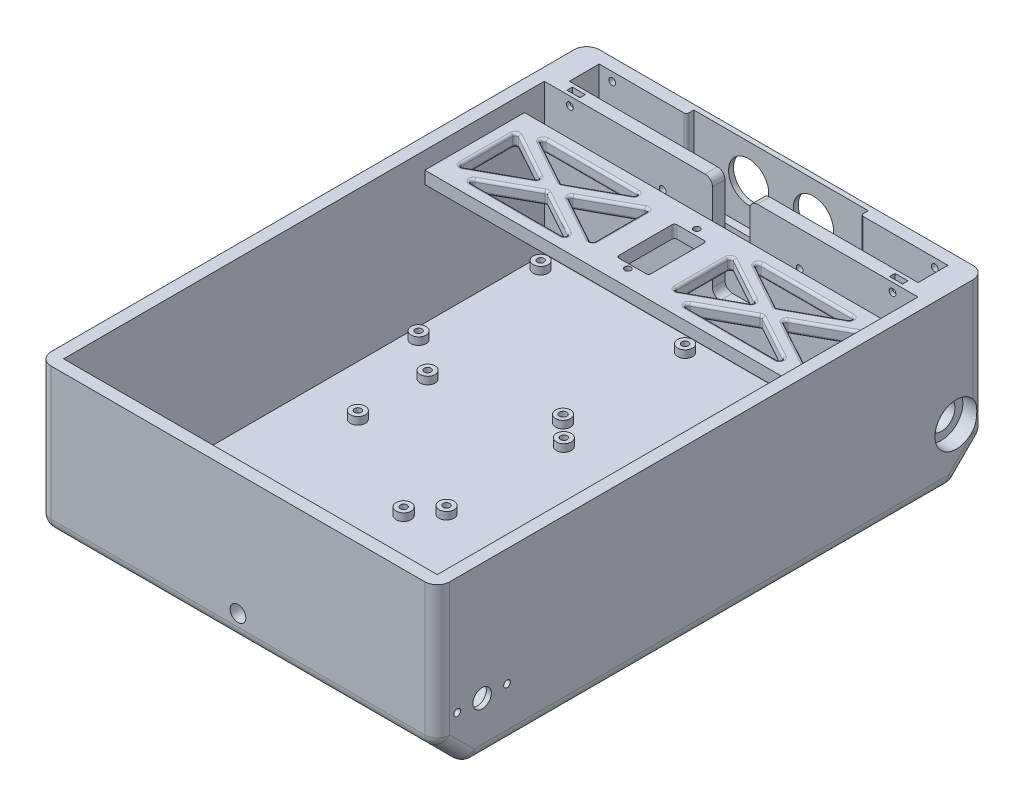
SolidWorks part; units mm, degrees
ref_plane "Front Plane" through (0, 0, 0) normal (0, 0, 1) x (1, 0, 0)
ref_plane "Top Plane" through (0, 0, 0) normal (0, 1, 0) x (1, 0, 0)
ref_plane "Right Plane" through (0, 0, 0) normal (1, 0, 0) x (0, 0, -1)
sketch "Main Body" plane through (0, 0, 0) normal (0, 1, 0) x (1, 0, 0)
  line L0 (-75, 110) -> (75, 110)
  line L1 (-75, -105) -> (75, -105)
  line L2 (-75, -105) -> (-75, 105)
  line L3 (-75, 105) -> (75, 105)
  line L4 (75, -105) -> (75, 105)
  line L5 (-75, -105) -> (75, 105) construction
  line L6 (-75, 105) -> (75, -105) construction
  line L7 (80, -105) -> (80, 105)
  line L8 (-75, -110) -> (75, -110)
  line L9 (-80, -105) -> (-80, 105)
  line L10 (-80, -110) -> (80, -110) construction
  line L11 (-80, -110) -> (-80, 110) construction
  line L12 (80, -110) -> (80, 110) construction
  line L13 (-80, 110) -> (80, 110) construction
  arc A0 (-75, -110) -> (-80, -105) centre (-75, -105) cw
  arc A1 (80, -105) -> (75, -110) centre (75, -105) cw
  arc A2 (75, 110) -> (80, 105) centre (75, 105) cw
  arc A3 (-75, 110) -> (-80, 105) centre (-75, 105) ccw
  point P0 (0, 0)
  dimension "D4" = 5
  dimension "D1" = 75
  dimension "D2" = 210
  dimension "D3" = 5
extrude "Boss-Extrude1" add sketch "Main Body" along normal blind 8 contours L1 L4 L3 L2 | L9 L8 L7 L0 L4 L1 L2 L3 region at (0, 0, -107.2797) region at (0, 0, 0)
extrude "Boss-Extrude3" add sketch "Main Body<4>" along normal blind 60 from surface starting at face at (0, 8, 0)
sketch "Main Body<4>" plane through (0, 0, 0) normal (0, 1, 0) x (1, 0, 0) same geometry as "Main Body"
sketch "Sketch1" plane through (75, 0, 0) normal (-1, 0, 0) x (0, 0, 1)
  line L0 (105, 68) -> (105, 8) construction
  line L1 (-105, 8) -> (105, 8) construction
  line L2 (79, 15.5) -> (105, 15.5)
  line L3 (79, 8) -> (105, 8)
  line L4 (79, 8) -> (79, 34)
  line L5 (79, 34) -> (105, 34)
  line L6 (105, 8) -> (105, 34)
  line L7 (79, 8) -> (105, 34) construction
  line L8 (79, 34) -> (105, 8) construction
  circle A0 centre (92, 21) radius 13
  line M2 (-105, 8) -> (105, 8)
  line M3 (105, 8) -> (105, 68)
  dimension "D1" = 26
  dimension "D2" = 7.5
extrude "Boss-Extrude4" add sketch "Sketch1" along normal up to surface (150 mm away) contours A0 L4 M2 | A0 L3 M3 region at (75, 10.5201, 82.0674) region at (75, 10.5201, 101.9326) up to face at (-75, 38, 0)
sketch "Sketch2" plane through (0, 0, 0) normal (1, 0, 0) x (0, 0, -1)
  line L0 (-105, 68) -> (-105, 15.5) construction
  line L1 (-105, 8) -> (-79, 8)
  line L2 (-105, 8) -> (-105, 15.5)
  line L3 (-105, 15.5) -> (-79, 15.5)
  line L4 (-79, 8) -> (-79, 15.5)
  line L5 (105, 8) -> (-79, 8) construction
  line L6 (-79, 8) -> (-79, 15.5) construction
  line L7 (-79, 15.5) -> (-80.2208, 15.5) construction
extrude "Cut-Extrude1" cut sketch "Sketch2" against normal mid plane 12
sketch "Sketch3" plane through (0, 8, 0) normal (0, 1, 0) x (1, 0, 0)
  line L0 (75, -105) -> (-75, -105) construction
  line L1 (-4, -79) -> (-11, -79)
  line L2 (-4, -79) -> (-4, -105)
  line L3 (-4, -105) -> (-11, -105)
  line L4 (-11, -79) -> (-11, -105)
  line L5 (0, 0) -> (0, -105) construction
  line L6 (-75, -79) -> (-6, -79) construction
  line L7 (11, -79) -> (11, -105)
  line L8 (4, -105) -> (11, -105)
  line L9 (4, -79) -> (4, -105)
  line L10 (4, -79) -> (11, -79)
  line L11 (-6, -103.7792) -> (-6, -92) construction
  dimension "D1" = 5
  dimension "D2" = 4
extrude "Boss-Extrude5" add sketch "Sketch3" along normal blind 20
sketch "Sketch4" plane through (0, 8, 0) normal (0, 1, 0) x (1, 0, 0)
  line L0 (-75, -105) -> (-75, 105) construction
  line L1 (-75, 93) -> (75, 93)
  line L2 (-75, 93) -> (-75, 88)
  line L3 (-75, 88) -> (75, 88)
  line L4 (75, 93) -> (75, 88)
  line L5 (75, 105) -> (75, -105) construction
  line L6 (-75, 105) -> (75, 105) construction
  dimension "D1" = 17
  dimension "D2" = 5
extrude "Boss-Extrude6" add sketch "Sketch4" along normal up to surface (60 mm away) up to face at (0, 68, 0)
sketch "Sketch5" plane through (80, 0, 0) normal (1, 0, 0) x (0, 0, -1)
  circle A0 centre (-92, 21) radius 3.5 construction
  circle A1 centre (-92, 21) radius 3.5
  circle A2 centre (-92, 21) radius 3.7
  dimension "D1" = 0.2
extrude "Cut-Extrude4" cut sketch "Sketch5" against normal up to next contours A1 | A2 A1 region at (80, 21, 92) region at (80, 21, 95.5953)
sketch "Sketch6" plane through (-75, 0, 0) normal (1, 0, 0) x (0, 0, -1)
  circle A0 centre (-92, 21) radius 13
  dimension "D1" = 26
extrude "Cut-Extrude5" cut sketch "Sketch6" against normal offset from surface (3 mm away) 2 up to face at (-80, 34, 0)
mirror "Mirror1" about plane through (0, 0, 0) normal (1, 0, 0) of "Cut-Extrude4"
sketch "Sketch8" plane through (75, 0, 0) normal (-1, 0, 0) x (0, 0, 1)
  circle A0 centre (92, 21) radius 13
  dimension "D1" = 26
extrude "Cut-Extrude6" cut sketch "Sketch8" against normal offset from surface (3 mm away) 2 up to face at (80, 21, 88.3)
sketch "Sketch10" plane through (80, 0, 0) normal (1, 0, 0) x (0, 0, -1)
  circle A1 centre (-82, 21) radius 1.25
  circle A2 centre (-82, 21) radius 1.25
  circle A3 centre (-102, 21) radius 1.25
  circle A4 centre (-102, 21) radius 1.25
  circle A5 centre (-92, 21) radius 12.5
  circle A6 centre (-92, 21) radius 12.5
  circle A63 centre (-102, 21) radius 1.35
  circle A64 centre (-82, 21) radius 1.35
  dimension "D4" = 2.7
extrude "Cut-Extrude7" cut sketch "Sketch10" against normal up to next contours A2 | A64 A2 | A4 | A63 A4 region at (80, 21, 82) region at (80, 21, 102) region at (80, 21, 103.3118) region at (80, 21, 83.3118)
mirror "Mirror3" about plane through (0, 0, 0) normal (1, 0, 0) of "Cut-Extrude7"
sketch "Sketch11" plane through (80, 0, 0) normal (1, 0, 0) x (0, 0, -1)
  circle A0 centre (98.375, 21.05) radius 4.425 construction
  circle A1 centre (98.375, 21.05) radius 4.425
  circle A3 centre (98.375, 21.05) radius 5.425
  dimension "D1" = 1
extrude "Cut-Extrude10" cut sketch "Sketch11" against normal through all contours A1 | A3 A1 region at (80, 21.05, -98.375) region at (80, 21.05, -93.1034)
sketch "Sketch12" plane through (-75, 0, 0) normal (1, 0, 0) x (0, 0, -1)
  line L0 (93, 8) -> (105, 8) construction
  line L1 (93, 68) -> (105, 68)
  line L2 (93, 68) -> (93, 8)
  line L3 (93, 8) -> (105, 8)
  line L4 (105, 68) -> (105, 8)
  line L6 (93, 68) -> (93, 21.7848) construction
  line L7 (93, 68) -> (105, 68) construction
  circle A2 centre (98.375, 21.05) radius 5.425 construction
  circle A3 centre (98.375, 21.05) radius 5.425
  point P5 (0, 0)
extrude "Boss-Extrude7" add sketch "Sketch12" along normal blind 5 contours A3 L2 L3 L4 L1 region at (-75, 40.4958, -99.0916)
sketch "Sketch13" plane through (-80, 0, 0) normal (-1, 0, 0) x (0, 0, 1)
  circle A0 centre (-98.375, 21.05) radius 8.6
  circle A2 centre (-98.375, 21.05) radius 5.425 construction
  dimension "D1" = 17.2
extrude "Cut-Extrude11" cut sketch "Sketch13" against normal blind 6
mirror "Mirror4" about plane through (0, 0, 0) normal (1, 0, 0) of "Boss-Extrude7", "Cut-Extrude11"
sketch "Sketch14" plane through (0, 8, 0) normal (0, 1, 0) x (1, 0, 0)
  line L0 (-4, -105) -> (-4, -79) construction
  line L1 (-4, -95) -> (4, -95)
  line L2 (-4, -95) -> (-4, -105)
  line L3 (-4, -105) -> (4, -105)
  line L4 (4, -95) -> (4, -105)
  dimension "D1" = 10
extrude "Boss-Extrude9" add sketch "Sketch14" along normal blind 5
sketch "Sketch15" plane through (0, 0, 110) normal (0, 0, 1) x (1, 0, 0)
  arc A4 (3.15, 19.5) -> (-3.15, 19.5) centre (0, 19.5) ccw
  arc A5 (-3.15, 19.5) -> (3.15, 19.5) centre (0, 19.5) ccw
  arc A6 (3, 19.5) -> (-3, 19.5) centre (0, 19.5) ccw construction
  dimension "D1" = 3.15
extrude "Cut-Extrude12" cut sketch "Sketch15" against normal up to next contours A4 A5 region at (0, 19.5, 110)
sketch "Sketch16" plane through (0, 0, 0) normal (0, -1, 0) x (1, 0, 0)
  circle A0 centre (-12.5, -82) radius 1.475 construction
  circle A1 centre (-70.5, -82) radius 1.475 construction
  circle A2 centre (-70.5, -33) radius 1.475 construction
  circle A3 centre (-12.5, -33) radius 1.475 construction
  circle A4 centre (-4.2, -25) radius 1.475 construction
  circle A5 centre (-55, -21.12) radius 1.475 construction
  circle A6 centre (-55, 6.88) radius 1.475 construction
  circle A7 centre (-4.2, 22.08) radius 1.475 construction
  circle A8 centre (-12.3, 31.18) radius 1.475 construction
  circle A9 centre (24.2, 31.18) radius 1.475 construction
  circle A10 centre (37.8459, 24.117) radius 1.475 construction
  circle A11 centre (59.5541, 24.117) radius 1.475 construction
  circle A12 centre (59.5541, 68.243) radius 1.475 construction
  circle A13 centre (37.8459, 68.243) radius 1.475 construction
  circle A14 centre (24.2, 67.68) radius 1.475 construction
  circle A15 centre (-12.3, 67.68) radius 1.475 construction
  circle A16 centre (-12.5, -82) radius 1.475
  circle A17 centre (-70.5, -82) radius 1.475
  circle A18 centre (-70.5, -33) radius 1.475
  circle A19 centre (-12.5, -33) radius 1.475
  circle A20 centre (-4.2, -25) radius 1.475
  circle A21 centre (-55, -21.12) radius 1.475
  circle A22 centre (-55, 6.88) radius 1.475
  circle A23 centre (-4.2, 22.08) radius 1.475
  circle A24 centre (-12.3, 31.18) radius 1.475
  circle A25 centre (24.2, 31.18) radius 1.475
  circle A26 centre (37.8459, 24.117) radius 1.475
  circle A27 centre (59.5541, 24.117) radius 1.475
  circle A28 centre (59.5541, 68.243) radius 1.475
  circle A29 centre (37.8459, 68.243) radius 1.475
  circle A30 centre (24.2, 67.68) radius 1.475
  circle A31 centre (-12.3, 67.68) radius 1.475
  circle A32 centre (-70.5, -82) radius 1.35
  circle A33 centre (-12.5, -82) radius 1.35
  circle A34 centre (-12.5, -33) radius 1.35
  circle A35 centre (-4.2, -25) radius 1.35
  circle A36 centre (-55, -21.12) radius 1.35
  circle A37 centre (-70.5, -33) radius 1.35
  circle A38 centre (-55, 6.88) radius 1.35
  circle A39 centre (-12.3, 31.18) radius 1.35
  circle A40 centre (-4.2, 22.08) radius 1.35
  circle A41 centre (24.2, 31.18) radius 1.35
  circle A42 centre (37.8459, 24.117) radius 1.35
  circle A43 centre (59.5541, 24.117) radius 1.35
  circle A44 centre (37.8459, 68.243) radius 1.35
  circle A45 centre (59.5541, 68.243) radius 1.35
  circle A46 centre (24.2, 67.68) radius 1.35
  circle A47 centre (-12.3, 67.68) radius 1.35
  dimension "D1" = 2.7
extrude "Cut-Extrude13" cut sketch "Sketch16" against normal up to next contours A47 | A46 | A44 | A45 | A35 | A37 | A36 | A38 | A39 | A40 | A41 | A42 | A43 | A32 | A33 | A19 region at (-70.5, 0, -82) region at (-12.5, 0, -82) region at (-4.2, 0, -25) region at (-55, 0, -21.12) region at (-70.5, 0, -33) region at (-55, 0, 6.88) region at (-12.3, 0, 31.18) region at (-4.2, 0, 22.08) region at (24.2, 0, 31.18) region at (37.8459, 0, 24.117) region at (59.5541, 0, 24.117) region at (37.8459, 0, 68.243) region at (59.5541, 0, 68.243) region at (24.2, 0, 67.68) region at (-12.3, 0, 67.68)
sketch "Sketch18" plane through (75, 0, 0) normal (-1, 0, 0) x (0, 0, 1)
  line L1 (-80, 61.1) -> (-40, 61.1)
  line L2 (-80, 61.1) -> (-80, 56.1)
  line L3 (-80, 56.1) -> (-40, 56.1)
  line L4 (-40, 61.1) -> (-40, 56.1)
  line L5 (-88, 68) -> (105, 68) construction
  dimension "D1" = 5
  dimension "D2" = 30
  dimension "D3" = 40
  dimension "D4" = 6.9
extrude "Boss-Extrude11" add sketch "Sketch18" along normal up to next
sketch "Sketch19" plane through (0, 68, 0) normal (0, 1, 0) x (1, 0, 0)
  line L1 (-6.425, 71.625) -> (6.425, 71.625)
  line L2 (-6.425, 71.625) -> (-6.425, 48.375)
  line L3 (-6.425, 48.375) -> (6.425, 48.375)
  line L4 (6.425, 71.625) -> (6.425, 48.375)
  line L12 (-75, 80) -> (-75, 40)
  line L13 (-75, 40) -> (75, 40)
  line L14 (75, 40) -> (75, 80)
  line L15 (75, 80) -> (-75, 80)
  line L16 (-75, 80) -> (-75, 40)
  line L17 (-75, 40) -> (75, 40)
  line L18 (75, 40) -> (75, 80)
  line L19 (75, 80) -> (-75, 80)
  point P4 (0, 71.625)
  point P8 (0, 80)
  point P12 (6.425, 60)
  point P13 (75, 60)
  dimension "D1" = 23.25
  dimension "D2" = 12.85
  dimension "D3" = 0
extrude "Cut-Extrude14" cut sketch "Sketch19" against normal up to next contours L4 L1 L2 L3 region at (0, 68, -60)
sketch "Sketch21" plane through (0, 0, -110) normal (0, 0, -1) x (-1, 0, 0)
  circle A1 centre (-64.75, 64.5) radius 1.3
  circle A2 centre (-64.75, 64.5) radius 1.3
  circle A3 centre (64.75, 64.5) radius 1.3
  circle A4 centre (64.75, 64.5) radius 1.3
  circle A44 centre (-64.75, 64.5) radius 1.35
  circle A45 centre (64.75, 64.5) radius 1.35
  dimension "D3" = 2.7
extrude "Cut-Extrude16" cut sketch "Sketch21" against normal up to surface (22 mm away) contours A44 A2 | A2 | A45 A4 | A4 region at (64.75, 64.5, -110) region at (-64.75, 64.5, -110) region at (66.0618, 64.5, -110) region at (-63.4382, 64.5, -110) up to face at (0, 38, -88)
ref_plane "Plane1" through (0, 0, -90.5) normal (0, 0, -1) x (-1, 0, 0)
sketch "Sketch22" plane through (0, 0, -90.5) normal (0, 0, -1) x (-1, 0, 0)
  line L0 (-67.35, 66.0011) -> (-67.35, 68)
  line L1 (-62.15, 66.0011) -> (-64.75, 67.5022)
  line L2 (-64.75, 67.5022) -> (-67.35, 66.0011)
  line L3 (-67.35, 66.0011) -> (-67.35, 62.9989)
  line L4 (-67.35, 62.9989) -> (-64.75, 61.4978)
  line L5 (-64.75, 61.4978) -> (-62.15, 62.9989)
  line L6 (-62.15, 62.9989) -> (-62.15, 66.0011)
  line L7 (-67.35, 68) -> (-62.15, 68)
  line L8 (-62.15, 68) -> (-62.15, 66.0011)
  line L9 (70, 68) -> (-70, 68) construction
  line L10 (0, 0) -> (0, 68) construction
  line L11 (75, 68) -> (-75, 68) construction
  line L12 (64.75, 61.4978) -> (62.15, 62.9989)
  line L13 (67.35, 62.9989) -> (64.75, 61.4978)
  line L14 (64.75, 67.5022) -> (67.35, 66.0011)
  line L15 (67.35, 66.0011) -> (67.35, 62.9989)
  line L16 (67.35, 66.0011) -> (67.35, 68)
  line L17 (62.15, 62.9989) -> (62.15, 66.0011)
  line L18 (62.15, 68) -> (62.15, 66.0011)
  line L19 (67.35, 68) -> (62.15, 68)
  line L20 (62.15, 66.0011) -> (64.75, 67.5022)
  circle A0 centre (-64.75, 64.5) radius 2.6 construction
  circle A1 centre (-64.75, 64.5) radius 1.35 construction
  dimension "D1" = 5.2
extrude "Cut-Extrude17" cut sketch "Sketch22" against normal mid plane 2.2 contours L20 L17 L12 L13 L15 L14 | L18 L20 L14 L16 L19 | L5 L6 L1 L2 L3 L4 | L8 L7 L0 L2 L1 region at (67.2943, 67.0006, -90.5) region at (64.75, 64.5, -90.5) region at (-64.75, 64.5, -90.5) region at (-62.2057, 67.0006, -90.5)
sketch "Sketch23" plane through (0, 0, -110) normal (0, 0, -1) x (-1, 0, 0)
  circle A0 centre (64.75, 64.5) radius 2.5
  circle A1 centre (-64.75, 64.5) radius 2.5
  circle A2 centre (64.75, 64.5) radius 1.35 construction
  circle A3 centre (-64.75, 64.5) radius 1.35 construction
  dimension "D1" = 5
  dimension "D2" = 5
extrude "Cut-Extrude18" cut sketch "Sketch23" against normal mid plane 2.5
sketch "Sketch24" plane through (0, 61.1, 0) normal (0, 1, 0) x (1, 0, 0)
  circle A0 centre (0, 46.475) radius 1.2502
  arc A1 (0.4, 45.5583) -> (-0.4, 45.5583) centre (0, 46.475) ccw construction
  circle A2 centre (0, 74.175) radius 1.2502
  arc A3 (-0.4, 75.0917) -> (0, 73.1748) centre (0, 74.175) ccw construction
  point P5 (0.4, 45.5583)
  dimension "D1" = 0.25
extrude "Cut-Extrude19" cut sketch "Sketch24" against normal up to next
sketch "Sketch25" plane through (0, 61.1, 0) normal (0, 1, 0) x (1, 0, 0)
  line L1 (-11.3, 80) -> (11.3, 80)
  line L2 (-11.3, 80) -> (-11.3, 40)
  line L3 (-11.3, 40) -> (11.3, 40)
  line L4 (-75, 80) -> (-75, 40)
  line L5 (-75, 40) -> (75, 40)
  line L6 (75, 40) -> (75, 80)
  line L7 (75, 80) -> (-75, 80)
  line L8 (-75, 80) -> (-75, 40)
  line L9 (-75, 40) -> (75, 40)
  line L10 (75, 40) -> (75, 80)
  line L11 (75, 80) -> (-75, 80)
  line L12 (11.3, 80) -> (11.3, 40)
  line L13 (-11.3, 80) -> (11.3, 40) construction
  line L14 (-11.3, 40) -> (11.3, 80) construction
  line L15 (0, 80) -> (0, 40) construction
  line L16 (70, 75) -> (70, 45)
  line L17 (-70, 75) -> (-16.3, 75)
  line L18 (-70, 75) -> (-70, 45)
  line L19 (-70, 45) -> (-16.3, 45)
  line L20 (-16.3, 75) -> (-16.3, 45)
  line L21 (-70, 75) -> (-16.3, 45) construction
  line L22 (-70, 45) -> (-16.3, 75) construction
  line L23 (70, 75) -> (16.3, 45) construction
  line L24 (70, 45) -> (16.3, 75) construction
  line L25 (70, 75) -> (16.3, 75)
  line L26 (16.3, 75) -> (16.3, 45)
  line L27 (70, 45) -> (16.3, 45)
  line L28 (-75, 60) -> (-11.3, 60) construction
  line L29 (75, 60) -> (11.3, 60) construction
  line L30 (-70, 71.9362) -> (-48.3314, 60)
  line L31 (-16.3, 71.9362) -> (-37.9686, 60)
  line L32 (70, 71.9362) -> (48.3314, 60)
  line L33 (-48.3314, 60) -> (-70, 48.0638)
  line L34 (48.3314, 60) -> (70, 48.0638)
  line L35 (-65.199, 45) -> (-43.15, 57.1458)
  line L36 (65.199, 45) -> (43.15, 57.1458)
  line L37 (-43.15, 57.1458) -> (-21.101, 45)
  line L38 (43.15, 57.1458) -> (21.101, 45)
  line L39 (16.3, 71.9362) -> (37.9686, 60)
  line L40 (-37.9686, 60) -> (-16.3, 48.0638)
  line L41 (37.9686, 60) -> (16.3, 48.0638)
  line L42 (-65.199, 75) -> (-43.15, 62.8542)
  line L43 (65.199, 75) -> (43.15, 62.8542)
  line L44 (-43.15, 62.8542) -> (-21.101, 75)
  line L45 (43.15, 62.8542) -> (21.101, 75)
  line L46 (-75, 40) -> (-75, 80) construction
  line L47 (-75, 40) -> (75, 40) construction
  point P2 (0, 60)
  point P9 (-43.15, 60)
  point P10 (75, 60)
  point P24 (43.15, 60)
  point P62 (-54.1745, 68.9271)
  dimension "D2" = 150
  dimension "D3" = 5
  dimension "D4" = 5
  dimension "D5" = 5
  dimension "D6" = 26.6686
  dimension "D7" = 140.199
  dimension "D1" = 0
extrude "Cut-Extrude21" cut sketch "Sketch25" against normal up to next contours L37 L35 L19 | L33 L30 L18 | L42 L44 L17 | L31 L40 L20 | L41 L39 L26 | L45 L43 L25 | L36 L38 L27 | L32 L34 L16 region at (62.7771, 61.1, -60) region at (43.15, 61.1, -70.9514) region at (43.15, 61.1, -49.0486) region at (23.5229, 61.1, -60) region at (-43.15, 61.1, -70.9514) region at (-62.7771, 61.1, -60) region at (-23.5229, 61.1, -60) region at (-43.15, 61.1, -49.0486)
sketch "Sketch26" plane through (-80, 0, 0) normal (-1, 0, 0) x (0, 0, 1)
  line L0 (-110, 12.6843) -> (-97.3157, 0)
  line L1 (-110, 68) -> (-110, 0) construction
  line L2 (105, 0) -> (-105, 0) construction
  line L3 (-97.3157, 0) -> (-92.3157, 0)
  line L4 (-92.3157, 0) -> (-110, 17.6843)
  line L5 (-110, 17.6843) -> (-110, 12.6843)
  line L6 (-110, 12.6843) -> (-110, 0)
  line L7 (-110, 0) -> (-97.3157, 0)
  circle A1 centre (-98.375, 21.05) radius 8.6 construction
  line M5 (-105, 15.5664) -> (-105, 0)
  line M6 (-105, 0) -> (105, 0)
  dimension "D1" = 2
  dimension "D2" = 5
  dimension "D3" = 45
extrude "Cut-Extrude22" cut sketch "Sketch26" against normal up to next contours L6 L7 L0 M5 | L0 M5 M6 region at (-80, 5.1944, -107.7046) region at (-80, 2.5614, -102.4386)
mirror "Mirror5" about plane through (0, 0, 0) normal (0, 0, 1) of "Cut-Extrude22"
fillet "Fillet1" radius 5 14 edges at (80, 3.8422, -101.1578) (78.5355, 11.2199, -108.5355) (-80, 3.8422, -101.1578) (-78.5355, 11.2199, -108.5355) (80, 3.8422, 101.1578) (78.5355, 11.2199, 108.5355) (-80, 3.8422, 101.1578) (-78.5355, 11.2199, 108.5355) (0, 0, -97.3157) (0, 12.6843, -110) (0, 0, 97.3157) (0, 12.6843, 110) (-80, 0, 0) (80, 0, 0)
fillet "Fillet2" radius 1 76 edges at (-32.1255, 56.1, -51.0729) (-32.1255, 61.1, -51.0729) (-21.101, 58.6, -45) (-43.15, 61.1, -45) (-43.15, 56.1, -45) (-54.1745, 56.1, -51.0729) (-65.199, 58.6, -45) (-54.1745, 61.1, -51.0729) (-43.15, 58.6, -57.1458) (32.1255, 56.1, -68.9271) (32.1255, 61.1, -68.9271) (21.101, 58.6, -75) (43.15, 61.1, -75) (43.15, 56.1, -75) (54.1745, 56.1, -68.9271) (65.199, 58.6, -75) (54.1745, 61.1, -68.9271) (43.15, 58.6, -62.8542) (54.1745, 61.1, -51.0729) (54.1745, 56.1, -51.0729) (43.15, 56.1, -45) (65.199, 58.6, -45) (43.15, 61.1, -45) (21.101, 58.6, -45) (32.1255, 61.1, -51.0729) (43.15, 58.6, -57.1458) (32.1255, 56.1, -51.0729) (59.1657, 61.1, -65.9681) (59.1657, 56.1, -65.9681) (70, 56.1, -60) (70, 58.6, -71.9362) (70, 61.1, -60) (70, 58.6, -48.0638) (59.1657, 61.1, -54.0319) (48.3314, 58.6, -60) (59.1657, 56.1, -54.0319) (-54.1745, 61.1, -68.9271) (-54.1745, 56.1, -68.9271) (-43.15, 56.1, -75) (-65.199, 58.6, -75) (-43.15, 61.1, -75) (-21.101, 58.6, -75) (-32.1255, 61.1, -68.9271) (-43.15, 58.6, -62.8542) (-32.1255, 56.1, -68.9271) (-59.1657, 56.1, -54.0319) (-59.1657, 61.1, -54.0319) (-70, 58.6, -48.0638) (-70, 61.1, -60) (-70, 56.1, -60) (-59.1657, 56.1, -65.9681) (-70, 58.6, -71.9362) (-59.1657, 61.1, -65.9681) (-48.3314, 58.6, -60) (-27.1343, 61.1, -65.9681) (-27.1343, 56.1, -65.9681) (-16.3, 56.1, -60) (-16.3, 58.6, -71.9362) (-16.3, 61.1, -60) (-16.3, 58.6, -48.0638) (-27.1343, 61.1, -54.0319) (-37.9686, 58.6, -60) (-27.1343, 56.1, -54.0319) (27.1343, 56.1, -54.0319) (27.1343, 61.1, -54.0319) (16.3, 58.6, -48.0638) (16.3, 61.1, -60) (16.3, 56.1, -60) (27.1343, 56.1, -65.9681) (16.3, 58.6, -71.9362) (27.1343, 61.1, -65.9681) (37.9686, 58.6, -60) (6.425, 58.6, -48.375) (-6.425, 58.6, -48.375) (-6.425, 58.6, -71.625) (6.425, 58.6, -71.625)
sketch "Sketch33" plane through (0, 0, -110) normal (0, 0, -1) x (-1, 0, 0)
  circle A0 centre (-13, 53.9999) radius 8.075
  circle A1 centre (13, 53.9999) radius 8.075
  circle A2 centre (-13, 53.9999) radius 7.3 construction
  circle A3 centre (13, 53.9999) radius 7.3 construction
  dimension "D1" = 16.15
extrude "Cut-Extrude27" cut sketch "Sketch33" against normal up to next
sketch "Sketch34" plane through (0, 0, -93) normal (0, 0, -1) x (-1, 0, 0)
  circle A0 centre (27.525, 54) radius 1.35 construction
  circle A1 centre (27.525, 54) radius 1.35
  circle A2 centre (-27.525, 54) radius 1.35 construction
  circle A3 centre (-27.525, 54) radius 1.35
  circle A4 centre (-27.525, 54) radius 1.35
  circle A5 centre (27.525, 54) radius 1.35
  dimension "D1" = 2.7
  dimension "D2" = 2.7
extrude "Cut-Extrude28" cut sketch "Sketch34" against normal up to next contours A3 | A1 region at (-27.525, 54, -93) region at (27.525, 54, -93)
sketch "Sketch35" plane through (0, 68, 0) normal (0, 1, 0) x (1, 0, 0)
  line L0 (70, 93) -> (-70, 93) construction
  line L1 (-7.5, 93) -> (7.5, 93)
  line L2 (-7.5, 93) -> (-7.5, 88)
  line L3 (-7.5, 88) -> (7.5, 88)
  line L4 (7.5, 93) -> (7.5, 88)
  line L5 (-7.5, 93) -> (7.5, 88) construction
  line L6 (-7.5, 88) -> (7.5, 93) construction
  line L7 (-75, 88) -> (75, 88) construction
  point P0 (0, 90.5)
  dimension "D1" = 15
extrude "Cut-Extrude29" cut sketch "Sketch35" against normal offset from surface (41 mm away) 19 up to face at (-4.2, 8, -23.65)
fillet "Fillet4" radius 3 9 edges at (0, 8, 95) (-7.5, 28, 79) (-7.5, 28, 105) (7.5, 28, 105) (7.5, 28, 79) (-7.5, 68, -90.5) (7.5, 68, -90.5) (-7.5, 27, -90.5) (7.5, 27, -90.5)
fillet "Fillet5" radius 1 1 edges at (0, 13, 95)
sketch "Sketch36" plane through (0, 68, 0) normal (0, 1, 0) x (1, 0, 0)
  line L0 (-70, 105) -> (70, 105) construction
  line L1 (-35, 108) -> (35, 108)
  line L2 (-35, 108) -> (-35, 105)
  line L3 (-35, 105) -> (35, 105)
  line L4 (35, 108) -> (35, 105)
  line L5 (-75, 110) -> (75, 110) construction
  point P6 (0, 108)
  dimension "D1" = 70
  dimension "D2" = 2
extrude "Cut-Extrude30" cut sketch "Sketch36" against normal blind 30
fillet "Fillet6" radius 1 2 edges at (35, 53, -105) (-35, 53, -105)
sketch "Sketch37" plane through (0, 8, 0) normal (0, 1, 0) x (1, 0, 0)
  line L8 (-4, -79) -> (-4, -92)
  line L9 (-4, -92) -> (4, -92)
  line L10 (4, -92) -> (4, -79)
  line L11 (4, -79) -> (75, -79)
  line L12 (75, -79) -> (75, 88)
  line L13 (75, 88) -> (-75, 88)
  line L14 (-75, 88) -> (-75, -79)
  line L15 (-75, -79) -> (-4, -79)
  line L16 (-4, -79) -> (-4, -92)
  line L17 (-4, -92) -> (4, -92)
  line L18 (4, -92) -> (4, -79)
  line L19 (4, -79) -> (75, -79)
  line L20 (75, -79) -> (75, 88)
  line L21 (75, 88) -> (-75, 88)
  line L22 (-75, 88) -> (-75, -79)
  line L23 (-75, -79) -> (-4, -79)
  circle A0 centre (-12.5, 82) radius 1.35 construction
  circle A1 centre (-4.2, 25) radius 1.35 construction
  circle A2 centre (-12.5, 33) radius 1.475 construction
  circle A3 centre (-70.5, 33) radius 1.35 construction
  circle A4 centre (-55, 21.12) radius 1.35 construction
  circle A5 centre (-55, -6.88) radius 1.35 construction
  circle A6 centre (-12.3, -31.18) radius 1.35 construction
  circle A7 centre (-4.2, -22.08) radius 1.35 construction
  circle A8 centre (24.2, -31.18) radius 1.35 construction
  circle A9 centre (37.8459, -24.117) radius 1.35 construction
  circle A10 centre (59.5541, -24.117) radius 1.35 construction
  circle A11 centre (59.5541, -68.243) radius 1.35 construction
  circle A12 centre (37.8459, -68.243) radius 1.35 construction
  circle A13 centre (24.2, -67.68) radius 1.35 construction
  circle A14 centre (-12.3, -67.68) radius 1.35 construction
  circle A15 centre (-70.5, 82) radius 1.35 construction
  circle A16 centre (-12.5, 82) radius 1.35
  circle A17 centre (-4.2, 25) radius 1.35
  circle A18 centre (-12.5, 33) radius 1.475
  circle A19 centre (-70.5, 33) radius 1.35
  circle A20 centre (-55, 21.12) radius 1.35
  circle A21 centre (-55, -6.88) radius 1.35
  circle A22 centre (-12.3, -31.18) radius 1.35
  circle A23 centre (-4.2, -22.08) radius 1.35
  circle A24 centre (24.2, -31.18) radius 1.35
  circle A25 centre (37.8459, -24.117) radius 1.35
  circle A26 centre (59.5541, -24.117) radius 1.35
  circle A27 centre (59.5541, -68.243) radius 1.35
  circle A28 centre (37.8459, -68.243) radius 1.35
  circle A29 centre (24.2, -67.68) radius 1.35
  circle A30 centre (-12.3, -67.68) radius 1.35
  circle A31 centre (-70.5, 82) radius 1.35
  circle A32 centre (-12.3, -67.68) radius 3
  circle A33 centre (24.2, -67.68) radius 3
  circle A34 centre (37.8459, -68.243) radius 3
  circle A35 centre (59.5541, -68.243) radius 3
  circle A36 centre (24.2, -31.18) radius 3
  circle A37 centre (37.8459, -24.117) radius 3
  circle A38 centre (59.5541, -24.117) radius 3
  circle A39 centre (-4.2, -22.08) radius 3
  circle A40 centre (-12.3, -31.18) radius 3
  circle A41 centre (-4.2, 25) radius 3
  circle A42 centre (-55, -6.88) radius 3
  circle A43 centre (-55, 21.12) radius 3
  circle A44 centre (-12.5, 33) radius 3
  circle A45 centre (-12.5, 82) radius 3
  circle A46 centre (-70.5, 82) radius 3
  circle A47 centre (-70.5, 33) radius 3
  circle M9 centre (-4.2, 25) radius 1.35
  circle M10 centre (59.5541, -68.243) radius 1.35
  circle M11 centre (37.8459, -68.243) radius 1.35
  circle M12 centre (24.2, -67.68) radius 1.35
  circle M13 centre (-70.5, 33) radius 1.35
  circle M14 centre (-55, 21.12) radius 1.35
  circle M15 centre (-55, -6.88) radius 1.35
  circle M16 centre (-12.3, -31.18) radius 1.35
  circle M17 centre (-4.2, -22.08) radius 1.35
  circle M18 centre (24.2, -31.18) radius 1.35
  circle M19 centre (37.8459, -24.117) radius 1.35
  circle M20 centre (59.5541, -24.117) radius 1.35
  circle M21 centre (-70.5, 82) radius 1.35
  circle M22 centre (-12.5, 82) radius 1.35
  circle M23 centre (-12.5, 33) radius 1.475
  circle M24 centre (-12.3, -67.68) radius 1.35
  dimension "D2" = 6
  dimension "D1" = 0
extrude "Boss-Extrude12" add sketch "Sketch37" along normal blind 3 contours A46 M21 | A45 M22 | A44 M23 | A41 M9 | A47 M13 | A43 M14 | A42 M15 | A38 M20 | A35 M10 | A34 M11 | A37 M19 | A36 M18 | A33 M12 | A39 M17 | A40 M16 | A32 M24 region at (-15.2151, 8, 67.68) region at (21.2849, 8, 67.68) region at (34.9307, 8, 68.243) region at (56.639, 8, 68.243) region at (21.2849, 8, 31.18) region at (34.9307, 8, 24.117) region at (56.639, 8, 24.117) region at (-7.1151, 8, 22.08) region at (-15.2151, 8, 31.18) region at (-7.1151, 8, -25) region at (-57.9151, 8, 6.88) region at (-57.9151, 8, -21.12) region at (-15.4151, 8, -33) region at (-15.4151, 8, -82) region at (-73.4151, 8, -82) region at (-73.4151, 8, -33)
equation "\"Screw\"= 2.7"
equation "\"D1@Sketch16\"=\"Screw\""
equation "\"D4@Sketch10\"=\"Screw\""
equation "\"D3@Sketch21\"=\"Screw\""
equation "\"D2@Sketch34\"=\"Screw\""
equation "\"D1@Sketch34\"=\"Screw\""
